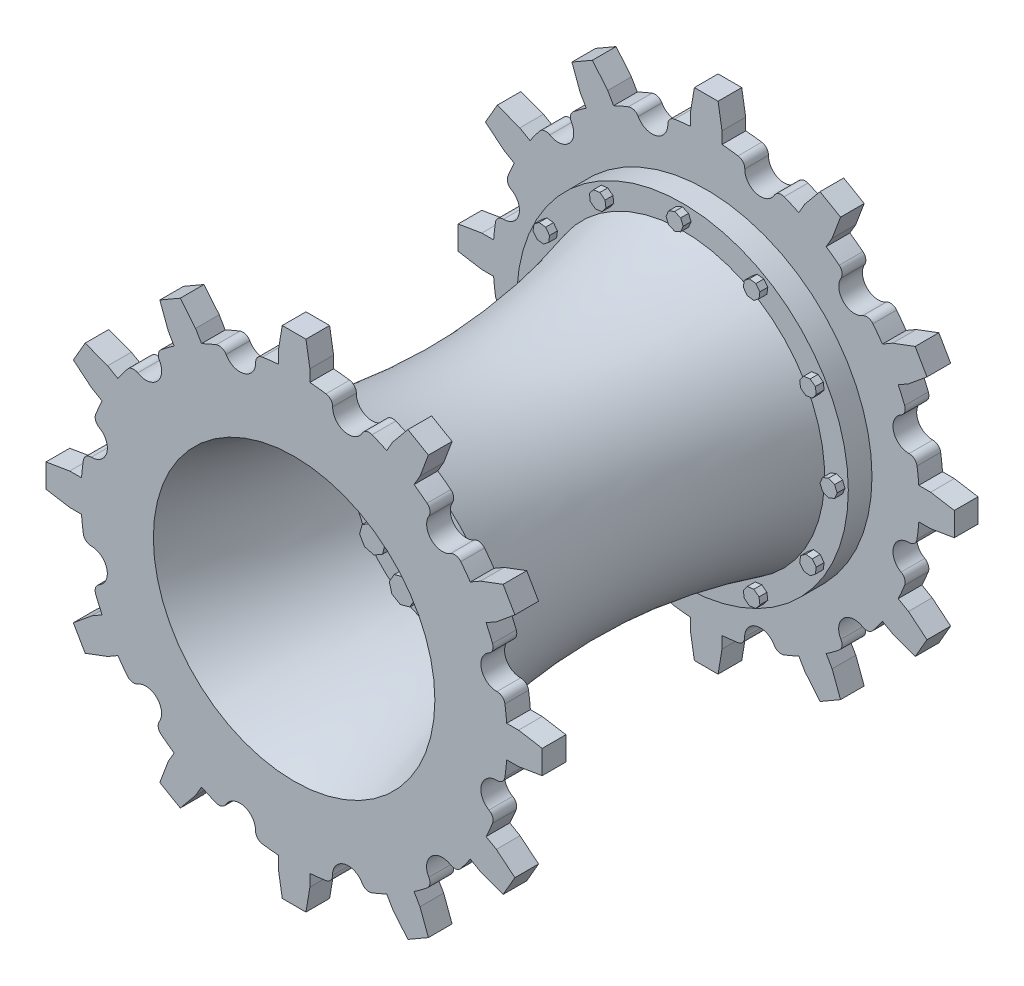
SolidWorks part; units mm, degrees
ref_plane "Ön Düzlem" through (0, 0, 0) normal (0, 0, 1) x (1, 0, 0)
ref_plane "Üst Düzlem" through (0, 0, 0) normal (0, 1, 0) x (1, 0, 0)
ref_plane "Sağ Düzlem" through (0, 0, 0) normal (1, 0, 0) x (0, 0, -1)
sketch "Çizim1" plane through (0, 0, 0) normal (0, 0, 1) x (1, 0, 0)
  line L2 (-20, 269.2582) -> (-20, 284.2582)
  line L3 (20, 269.2582) -> (20, 284.2582)
  line L4 (-20, 284.2582) -> (-15, 314.2582)
  line L5 (-15, 314.2582) -> (15, 314.2582)
  line L6 (15, 314.2582) -> (20, 284.2582)
  line L7 (117.3086, 243.1845) -> (124.8086, 256.1749)
  line L8 (151.9496, 223.1845) -> (159.4496, 236.1749)
  line L9 (124.8086, 256.1749) -> (144.1387, 279.6556)
  line L10 (144.1387, 279.6556) -> (170.1195, 264.6556)
  line L11 (170.1195, 264.6556) -> (159.4496, 236.1749)
  line L13 (223.1845, 151.9496) -> (236.1749, 159.4496)
  line L14 (243.1845, 117.3086) -> (256.1749, 124.8086)
  line L15 (236.1749, 159.4496) -> (264.6556, 170.1195)
  line L16 (264.6556, 170.1195) -> (279.6556, 144.1387)
  line L17 (279.6556, 144.1387) -> (256.1749, 124.8086)
  line L19 (269.2582, 20) -> (284.2582, 20)
  line L20 (269.2582, -20) -> (284.2582, -20)
  line L21 (284.2582, 20) -> (314.2582, 15)
  line L22 (314.2582, 15) -> (314.2582, -15)
  line L23 (314.2582, -15) -> (284.2582, -20)
  line L25 (243.1845, -117.3086) -> (256.1749, -124.8086)
  line L26 (223.1845, -151.9496) -> (236.1749, -159.4496)
  line L27 (256.1749, -124.8086) -> (279.6556, -144.1387)
  line L28 (279.6556, -144.1387) -> (264.6556, -170.1195)
  line L29 (264.6556, -170.1195) -> (236.1749, -159.4496)
  line L31 (151.9496, -223.1845) -> (159.4496, -236.1749)
  line L32 (117.3086, -243.1845) -> (124.8086, -256.1749)
  line L33 (159.4496, -236.1749) -> (170.1195, -264.6556)
  line L34 (170.1195, -264.6556) -> (144.1387, -279.6556)
  line L35 (144.1387, -279.6556) -> (124.8086, -256.1749)
  line L37 (20, -269.2582) -> (20, -284.2582)
  line L38 (-20, -269.2582) -> (-20, -284.2582)
  line L39 (20, -284.2582) -> (15, -314.2582)
  line L40 (15, -314.2582) -> (-15, -314.2582)
  line L41 (-15, -314.2582) -> (-20, -284.2582)
  line L43 (-117.3086, -243.1845) -> (-124.8086, -256.1749)
  line L44 (-151.9496, -223.1845) -> (-159.4496, -236.1749)
  line L45 (-124.8086, -256.1749) -> (-144.1387, -279.6556)
  line L46 (-144.1387, -279.6556) -> (-170.1195, -264.6556)
  line L47 (-170.1195, -264.6556) -> (-159.4496, -236.1749)
  line L49 (-223.1845, -151.9496) -> (-236.1749, -159.4496)
  line L50 (-243.1845, -117.3086) -> (-256.1749, -124.8086)
  line L51 (-236.1749, -159.4496) -> (-264.6556, -170.1195)
  line L52 (-264.6556, -170.1195) -> (-279.6556, -144.1387)
  line L53 (-279.6556, -144.1387) -> (-256.1749, -124.8086)
  line L55 (-269.2582, -20) -> (-284.2582, -20)
  line L56 (-269.2582, 20) -> (-284.2582, 20)
  line L57 (-284.2582, -20) -> (-314.2582, -15)
  line L58 (-314.2582, -15) -> (-314.2582, 15)
  line L59 (-314.2582, 15) -> (-284.2582, 20)
  line L61 (-243.1845, 117.3086) -> (-256.1749, 124.8086)
  line L62 (-223.1845, 151.9496) -> (-236.1749, 159.4496)
  line L63 (-256.1749, 124.8086) -> (-279.6556, 144.1387)
  line L64 (-279.6556, 144.1387) -> (-264.6556, 170.1195)
  line L65 (-264.6556, 170.1195) -> (-236.1749, 159.4496)
  line L67 (-151.9496, 223.1845) -> (-159.4496, 236.1749)
  line L68 (-117.3086, 243.1845) -> (-124.8086, 256.1749)
  line L69 (-159.4496, 236.1749) -> (-170.1195, 264.6556)
  line L70 (-170.1195, 264.6556) -> (-144.1387, 279.6556)
  line L71 (-144.1387, 279.6556) -> (-124.8086, 256.1749)
  line L73 (20, 269.2582) -> (117.6795, 243.8269) construction
  arc A0 (40.3386, 266.9697) -> (20, 269.2582) centre (0, 0) ccw
  arc A1 (48.843, 256.9021) -> (86.3302, 246.8429) centre (68.8397, 256.5425) ccw
  arc A2 (98.7322, 251.3005) -> (86.3302, 246.8429) centre (95.0755, 241.9931) ccw
  arc A3 (48.843, 256.9021) -> (40.3386, 266.9697) centre (38.8446, 257.0819) ccw
  arc A4 (170.7503, 198.0623) -> (168.4191, 211.0332) centre (162.1813, 203.2171) ccw
  arc A5 (170.7503, 198.0623) -> (198.1856, 170.6071) centre (187.8882, 187.7525) ccw
  arc A6 (211.1549, 168.2665) -> (198.1856, 170.6071) centre (203.3343, 162.0344) ccw
  arc A7 (246.9052, 86.1518) -> (251.3718, 98.5506) centre (242.0617, 94.9005) ccw
  arc A8 (246.9052, 86.1518) -> (256.9373, 48.6573) centre (256.5922, 68.6543) ccw
  arc A9 (266.9987, 40.1456) -> (256.9373, 48.6573) centre (257.1099, 38.6588) ccw
  arc A10 (256.9021, -48.843) -> (266.9697, -40.3386) centre (257.0819, -38.8446) ccw
  arc A11 (256.9021, -48.843) -> (246.8429, -86.3302) centre (256.5425, -68.8397) ccw
  arc A12 (251.3005, -98.7322) -> (246.8429, -86.3302) centre (241.9931, -95.0755) ccw
  arc A13 (198.0623, -170.7503) -> (211.0332, -168.4191) centre (203.2171, -162.1813) ccw
  arc A14 (198.0623, -170.7503) -> (170.6071, -198.1856) centre (187.7525, -187.8882) ccw
  arc A15 (168.2665, -211.1549) -> (170.6071, -198.1856) centre (162.0344, -203.3343) ccw
  arc A16 (86.1518, -246.9052) -> (98.5506, -251.3718) centre (94.9005, -242.0617) ccw
  arc A17 (86.1518, -246.9052) -> (48.6573, -256.9373) centre (68.6543, -256.5922) ccw
  arc A18 (40.1456, -266.9987) -> (48.6573, -256.9373) centre (38.6588, -257.1099) ccw
  arc A19 (-48.843, -256.9021) -> (-40.3386, -266.9697) centre (-38.8446, -257.0819) ccw
  arc A20 (-48.843, -256.9021) -> (-86.3302, -246.8429) centre (-68.8397, -256.5425) ccw
  arc A21 (-98.7322, -251.3005) -> (-86.3302, -246.8429) centre (-95.0755, -241.9931) ccw
  arc A22 (-170.7503, -198.0623) -> (-168.4191, -211.0332) centre (-162.1813, -203.2171) ccw
  arc A23 (-170.7503, -198.0623) -> (-198.1856, -170.6071) centre (-187.8882, -187.7525) ccw
  arc A24 (-211.1549, -168.2665) -> (-198.1856, -170.6071) centre (-203.3343, -162.0344) ccw
  arc A25 (-246.9052, -86.1518) -> (-251.3718, -98.5506) centre (-242.0617, -94.9005) ccw
  arc A26 (-246.9052, -86.1518) -> (-256.9373, -48.6573) centre (-256.5922, -68.6543) ccw
  arc A27 (-266.9987, -40.1456) -> (-256.9373, -48.6573) centre (-257.1099, -38.6588) ccw
  arc A28 (-256.9021, 48.843) -> (-266.9697, 40.3386) centre (-257.0819, 38.8446) ccw
  arc A29 (-256.9021, 48.843) -> (-246.8429, 86.3302) centre (-256.5425, 68.8397) ccw
  arc A30 (-251.3005, 98.7322) -> (-246.8429, 86.3302) centre (-241.9931, 95.0755) ccw
  arc A31 (-198.0623, 170.7503) -> (-211.0332, 168.4191) centre (-203.2171, 162.1813) ccw
  arc A32 (-198.0623, 170.7503) -> (-170.6071, 198.1856) centre (-187.7525, 187.8882) ccw
  arc A33 (-168.2665, 211.1549) -> (-170.6071, 198.1856) centre (-162.0344, 203.3343) ccw
  arc A34 (-86.1518, 246.9052) -> (-98.5506, 251.3718) centre (-94.9005, 242.0617) ccw
  arc A35 (-86.1518, 246.9052) -> (-48.6573, 256.9373) centre (-68.6543, 256.5922) ccw
  arc A36 (-40.1456, 266.9987) -> (-48.6573, 256.9373) centre (-38.6588, 257.1099) ccw
  arc A37 (-98.5506, 251.3718) -> (-117.3086, 243.1845) centre (0, 0) ccw
  arc A38 (-211.0332, 168.4191) -> (-223.1845, 151.9496) centre (0, 0) ccw
  arc A39 (-266.9697, 40.3386) -> (-269.2582, 20) centre (0, 0) ccw
  arc A40 (-243.1845, 117.3086) -> (-251.3005, 98.7322) centre (0, 0) ccw
  arc A41 (-151.9496, 223.1845) -> (-168.2665, 211.1549) centre (0, 0) ccw
  arc A42 (-269.2582, -20) -> (-266.9987, -40.1456) centre (0, 0) ccw
  arc A43 (-251.3718, -98.5506) -> (-243.1845, -117.3086) centre (0, 0) ccw
  arc A44 (-223.1845, -151.9496) -> (-211.1549, -168.2665) centre (0, 0) ccw
  arc A45 (-168.4191, -211.0332) -> (-151.9496, -223.1845) centre (0, 0) ccw
  arc A46 (-117.3086, -243.1845) -> (-98.7322, -251.3005) centre (0, 0) ccw
  arc A47 (-40.3386, -266.9697) -> (-20, -269.2582) centre (0, 0) ccw
  arc A48 (20, -269.2582) -> (40.1456, -266.9987) centre (0, 0) ccw
  arc A49 (98.5506, -251.3718) -> (117.3086, -243.1845) centre (0, 0) ccw
  arc A50 (151.9496, -223.1845) -> (168.2665, -211.1549) centre (0, 0) ccw
  arc A51 (211.0332, -168.4191) -> (223.1845, -151.9496) centre (0, 0) ccw
  arc A52 (243.1845, -117.3086) -> (251.3005, -98.7322) centre (0, 0) ccw
  arc A53 (266.9697, -40.3386) -> (269.2582, -20) centre (0, 0) ccw
  arc A54 (269.2582, 20) -> (266.9987, 40.1456) centre (0, 0) ccw
  arc A55 (251.3718, 98.5506) -> (243.1845, 117.3086) centre (0, 0) ccw
  arc A56 (223.1845, 151.9496) -> (211.1549, 168.2665) centre (0, 0) ccw
  arc A57 (168.4191, 211.0332) -> (151.9496, 223.1845) centre (0, 0) ccw
  arc A58 (117.3086, 243.1845) -> (98.7322, 251.3005) centre (0, 0) ccw
  arc A59 (-20, 269.2582) -> (-40.1456, 266.9987) centre (0, 0) ccw
  point P8 (0, 270)
  point P21 (135, 233.8269)
  point P30 (233.8269, 135)
  point P39 (270, 0)
  point P48 (233.8269, -135)
  point P57 (135, -233.8269)
  point P66 (0, -270)
  point P75 (-135, -233.8269)
  point P84 (-233.8269, -135)
  point P93 (-270, 0)
  point P102 (-233.8269, 135)
  point P111 (-135, 233.8269)
  point P117 (0, 0)
  point P200 (0, 0)
  dimension "D1" = 540
  dimension "D8" = 40
  dimension "D9" = 10
  dimension "D3" = 15
  dimension "D4" = 15
  dimension "D5" = 30
  dimension "D6" = 30
  dimension "D7" = 12
  dimension "D10" = 12
extrude "Yükseklik-Ekstrüzyon2" add sketch "Çizim1" along normal blind 30
sketch "Çizim2" plane through (0, 0, 30) normal (0, 0, 1) x (1, 0, 0)
  circle A0 centre (0, 0) radius 210
  dimension "D1" = 420
extrude "Yükseklik-Ekstrüzyon3" add sketch "Çizim2" along normal blind 30
sketch "Çizim3" plane through (0, 0, 60) normal (0, 0, 1) x (1, 0, 0)
  line L0 (-210, 0) -> (-180, 0) construction
  line L1 (-159.5012, 92.088) -> (-158.4198, 100.3014)
  line L2 (-184.1761, 0) -> (-187.3463, 7.6537)
  line L3 (-187.3463, 7.6537) -> (-195, 10.8239)
  line L4 (-195, 10.8239) -> (-202.6537, 7.6537)
  line L5 (-202.6537, 7.6537) -> (-205.8239, 0)
  line L6 (-205.8239, 0) -> (-202.6537, -7.6537)
  line L7 (-202.6537, -7.6537) -> (-195, -10.8239)
  line L8 (-195, -10.8239) -> (-187.3463, -7.6537)
  line L9 (-187.3463, -7.6537) -> (-184.1761, 0)
  line L10 (-158.4198, 100.3014) -> (-163.463, 106.8738)
  line L11 (-163.463, 106.8738) -> (-171.6764, 107.9551)
  line L12 (-171.6764, 107.9551) -> (-178.2487, 102.912)
  line L13 (-178.2487, 102.912) -> (-179.3301, 94.6986)
  line L14 (-179.3301, 94.6986) -> (-174.2869, 88.1262)
  line L15 (-174.2869, 88.1262) -> (-166.0735, 87.0449)
  line L16 (-166.0735, 87.0449) -> (-159.5012, 92.088)
  line L17 (-92.088, 159.5012) -> (-87.0449, 166.0735)
  line L18 (-87.0449, 166.0735) -> (-88.1262, 174.2869)
  line L19 (-88.1262, 174.2869) -> (-94.6986, 179.3301)
  line L20 (-94.6986, 179.3301) -> (-102.912, 178.2487)
  line L21 (-102.912, 178.2487) -> (-107.9551, 171.6764)
  line L22 (-107.9551, 171.6764) -> (-106.8738, 163.463)
  line L23 (-106.8738, 163.463) -> (-100.3014, 158.4198)
  line L24 (-100.3014, 158.4198) -> (-92.088, 159.5012)
  line L25 (0, 184.1761) -> (7.6537, 187.3463)
  line L26 (7.6537, 187.3463) -> (10.8239, 195)
  line L27 (10.8239, 195) -> (7.6537, 202.6537)
  line L28 (7.6537, 202.6537) -> (0, 205.8239)
  line L29 (0, 205.8239) -> (-7.6537, 202.6537)
  line L30 (-7.6537, 202.6537) -> (-10.8239, 195)
  line L31 (-10.8239, 195) -> (-7.6537, 187.3463)
  line L32 (-7.6537, 187.3463) -> (0, 184.1761)
  line L33 (92.088, 159.5012) -> (100.3014, 158.4198)
  line L34 (100.3014, 158.4198) -> (106.8738, 163.463)
  line L35 (106.8738, 163.463) -> (107.9551, 171.6764)
  line L36 (107.9551, 171.6764) -> (102.912, 178.2487)
  line L37 (102.912, 178.2487) -> (94.6986, 179.3301)
  line L38 (94.6986, 179.3301) -> (88.1262, 174.2869)
  line L39 (88.1262, 174.2869) -> (87.0449, 166.0735)
  line L40 (87.0449, 166.0735) -> (92.088, 159.5012)
  line L41 (159.5012, 92.088) -> (166.0735, 87.0449)
  line L42 (166.0735, 87.0449) -> (174.2869, 88.1262)
  line L43 (174.2869, 88.1262) -> (179.3301, 94.6986)
  line L44 (179.3301, 94.6986) -> (178.2487, 102.912)
  line L45 (178.2487, 102.912) -> (171.6764, 107.9551)
  line L46 (171.6764, 107.9551) -> (163.463, 106.8738)
  line L47 (163.463, 106.8738) -> (158.4198, 100.3014)
  line L48 (158.4198, 100.3014) -> (159.5012, 92.088)
  line L49 (184.1761, 0) -> (187.3463, -7.6537)
  line L50 (187.3463, -7.6537) -> (195, -10.8239)
  line L51 (195, -10.8239) -> (202.6537, -7.6537)
  line L52 (202.6537, -7.6537) -> (205.8239, 0)
  line L53 (205.8239, 0) -> (202.6537, 7.6537)
  line L54 (202.6537, 7.6537) -> (195, 10.8239)
  line L55 (195, 10.8239) -> (187.3463, 7.6537)
  line L56 (187.3463, 7.6537) -> (184.1761, 0)
  line L57 (159.5012, -92.088) -> (158.4198, -100.3014)
  line L58 (158.4198, -100.3014) -> (163.463, -106.8738)
  line L59 (163.463, -106.8738) -> (171.6764, -107.9551)
  line L60 (171.6764, -107.9551) -> (178.2487, -102.912)
  line L61 (178.2487, -102.912) -> (179.3301, -94.6986)
  line L62 (179.3301, -94.6986) -> (174.2869, -88.1262)
  line L63 (174.2869, -88.1262) -> (166.0735, -87.0449)
  line L64 (166.0735, -87.0449) -> (159.5012, -92.088)
  line L65 (92.088, -159.5012) -> (87.0449, -166.0735)
  line L66 (87.0449, -166.0735) -> (88.1262, -174.2869)
  line L67 (88.1262, -174.2869) -> (94.6986, -179.3301)
  line L68 (94.6986, -179.3301) -> (102.912, -178.2487)
  line L69 (102.912, -178.2487) -> (107.9551, -171.6764)
  line L70 (107.9551, -171.6764) -> (106.8738, -163.463)
  line L71 (106.8738, -163.463) -> (100.3014, -158.4198)
  line L72 (100.3014, -158.4198) -> (92.088, -159.5012)
  line L73 (0, -184.1761) -> (-7.6537, -187.3463)
  line L74 (-7.6537, -187.3463) -> (-10.8239, -195)
  line L75 (-10.8239, -195) -> (-7.6537, -202.6537)
  line L76 (-7.6537, -202.6537) -> (0, -205.8239)
  line L77 (0, -205.8239) -> (7.6537, -202.6537)
  line L78 (7.6537, -202.6537) -> (10.8239, -195)
  line L79 (10.8239, -195) -> (7.6537, -187.3463)
  line L80 (7.6537, -187.3463) -> (0, -184.1761)
  line L81 (-92.088, -159.5012) -> (-100.3014, -158.4198)
  line L82 (-100.3014, -158.4198) -> (-106.8738, -163.463)
  line L83 (-106.8738, -163.463) -> (-107.9551, -171.6764)
  line L84 (-107.9551, -171.6764) -> (-102.912, -178.2487)
  line L85 (-102.912, -178.2487) -> (-94.6986, -179.3301)
  line L86 (-94.6986, -179.3301) -> (-88.1262, -174.2869)
  line L87 (-88.1262, -174.2869) -> (-87.0449, -166.0735)
  line L88 (-87.0449, -166.0735) -> (-92.088, -159.5012)
  line L89 (-159.5012, -92.088) -> (-166.0735, -87.0449)
  line L90 (-166.0735, -87.0449) -> (-174.2869, -88.1262)
  line L91 (-174.2869, -88.1262) -> (-179.3301, -94.6986)
  line L92 (-179.3301, -94.6986) -> (-178.2487, -102.912)
  line L93 (-178.2487, -102.912) -> (-171.6764, -107.9551)
  line L94 (-171.6764, -107.9551) -> (-163.463, -106.8738)
  line L95 (-163.463, -106.8738) -> (-158.4198, -100.3014)
  line L96 (-158.4198, -100.3014) -> (-159.5012, -92.088)
  circle A0 centre (0, 0) radius 180 construction
  circle A1 centre (0, 0) radius 210 construction
  circle A2 centre (0, 0) radius 210 construction
  circle A3 centre (0, 0) radius 195 construction
  circle A4 centre (-195, 0) radius 10 construction
  circle A5 centre (-168.875, 97.5) radius 10 construction
  circle A6 centre (-97.5, 168.875) radius 10 construction
  circle A7 centre (0, 195) radius 10 construction
  circle A8 centre (97.5, 168.875) radius 10 construction
  circle A9 centre (168.875, 97.5) radius 10 construction
  circle A10 centre (195, 0) radius 10 construction
  circle A11 centre (168.875, -97.5) radius 10 construction
  circle A12 centre (97.5, -168.875) radius 10 construction
  circle A13 centre (0, -195) radius 10 construction
  circle A14 centre (-97.5, -168.875) radius 10 construction
  circle A15 centre (-168.875, -97.5) radius 10 construction
  point P10 (-195, 0)
  point P134 (0, 0)
  dimension "D1" = 360
  dimension "D2" = 20
  dimension "D3" = 12
extrude "Yükseklik-Ekstrüzyon4" add sketch "Çizim3" along normal blind 10
ref_plane "Düzlem1" through (0, 0, 252) normal (0, 0, 1) x (1, 0, 0)
sketch "Çizim15" plane through (0, 0, 0) normal (0, 0, -1) x (-1, 0, 0)
  circle A0 centre (0, 0) radius 45
  dimension "D1" = 90
extrude "Kes-Ekstrüzyon2" cut sketch "Çizim15" against normal blind 768
sketch "Çizim17" plane through (0, 0, 0) normal (1, 0, 0) x (0, 0, -1)
  line L0 (0, 0) -> (-776.2338, 0) construction
  line L1 (-60, 45) -> (-276, 45)
  line L2 (-60, 210) -> (-60, -210) construction
  line L3 (-276, 45) -> (-276, 150)
  line L4 (-60, 180) -> (-60, 45)
  arc A0 (-276, 150) -> (-60, 180) centre (-276, 942.6) ccw
  dimension "D1" = 180
  dimension "D2" = 45
  dimension "D3" = 216
  dimension "D4" = 150
revolve "Döndür2" add sketch "Çizim17" angle 360 about L0
mirror "Aynalama5" about plane through (0, 45, 276) normal (0, 0, 1) of bodies 121
sketch "Çizim18" plane through (0, 0, 0) normal (1, 0, 0) x (0, 0, -1)
  line L1 (-252, 0) -> (-642.2, 0)
  line L2 (-642.2, 0) -> (-642.2, 217.1923)
  line L3 (-252, 231) -> (-252, -231) construction
  line L4 (-252, 0) -> (-252, 130.3545)
  arc A2 (-497.4504, 160.757) -> (-54.5496, 160.757) centre (-276, 942.6) ccw
  arc A3 (-642.2, 217.1923) -> (-252, 130.3545) centre (-276, 942.6) ccw
  dimension "D1" = 20
revolve "Kes-Döndür2" cut sketch "Çizim18" angle 360 about L1
sketch "Çizim19" plane through (0, 0, 252) normal (0, 0, 1) x (1, 0, 0)
  circle A1 centre (0, 0) radius 130.3545
  circle A2 centre (0, 0) radius 130.3545
  dimension "D1" = 0
extrude "Yükseklik-Ekstrüzyon8" add sketch "Çizim19" along normal blind 96 contours A2
sketch "Çizim20" plane through (0, 0, 348) normal (0, 0, 1) x (1, 0, 0)
  line L0 (0, 130.3545) -> (0, 75) construction
  line L1 (67.4356, 86.8019) -> (64.2194, 98.8049)
  line L2 (15, 108.8905) -> (6.2132, 117.6772)
  line L3 (6.2132, 117.6772) -> (-6.2132, 117.6772)
  line L4 (-6.2132, 117.6772) -> (-15, 108.8905)
  line L5 (-15, 108.8905) -> (-15, 96.464)
  line L6 (-15, 96.464) -> (-6.2132, 87.6772)
  line L7 (-6.2132, 87.6772) -> (6.2132, 87.6772)
  line L8 (6.2132, 87.6772) -> (15, 96.464)
  line L9 (15, 96.464) -> (15, 108.8905)
  line L10 (64.2194, 98.8049) -> (53.4578, 105.0181)
  line L11 (53.4578, 105.0181) -> (41.4548, 101.8019)
  line L12 (41.4548, 101.8019) -> (35.2416, 91.0403)
  line L13 (35.2416, 91.0403) -> (38.4578, 79.0373)
  line L14 (38.4578, 79.0373) -> (49.2194, 72.8241)
  line L15 (49.2194, 72.8241) -> (61.2224, 76.0403)
  line L16 (61.2224, 76.0403) -> (67.4356, 86.8019)
  line L17 (101.8019, 41.4548) -> (105.0181, 53.4578)
  line L18 (105.0181, 53.4578) -> (98.8049, 64.2194)
  line L19 (98.8049, 64.2194) -> (86.8019, 67.4356)
  line L20 (86.8019, 67.4356) -> (76.0403, 61.2224)
  line L21 (76.0403, 61.2224) -> (72.8241, 49.2194)
  line L22 (72.8241, 49.2194) -> (79.0373, 38.4578)
  line L23 (79.0373, 38.4578) -> (91.0403, 35.2416)
  line L24 (91.0403, 35.2416) -> (101.8019, 41.4548)
  line L25 (108.8905, -15) -> (117.6772, -6.2132)
  line L26 (117.6772, -6.2132) -> (117.6772, 6.2132)
  line L27 (117.6772, 6.2132) -> (108.8905, 15)
  line L28 (108.8905, 15) -> (96.464, 15)
  line L29 (96.464, 15) -> (87.6772, 6.2132)
  line L30 (87.6772, 6.2132) -> (87.6772, -6.2132)
  line L31 (87.6772, -6.2132) -> (96.464, -15)
  line L32 (96.464, -15) -> (108.8905, -15)
  line L33 (86.8019, -67.4356) -> (98.8049, -64.2194)
  line L34 (98.8049, -64.2194) -> (105.0181, -53.4578)
  line L35 (105.0181, -53.4578) -> (101.8019, -41.4548)
  line L36 (101.8019, -41.4548) -> (91.0403, -35.2416)
  line L37 (91.0403, -35.2416) -> (79.0373, -38.4578)
  line L38 (79.0373, -38.4578) -> (72.8241, -49.2194)
  line L39 (72.8241, -49.2194) -> (76.0403, -61.2224)
  line L40 (76.0403, -61.2224) -> (86.8019, -67.4356)
  line L41 (41.4548, -101.8019) -> (53.4578, -105.0181)
  line L42 (53.4578, -105.0181) -> (64.2194, -98.8049)
  line L43 (64.2194, -98.8049) -> (67.4356, -86.8019)
  line L44 (67.4356, -86.8019) -> (61.2224, -76.0403)
  line L45 (61.2224, -76.0403) -> (49.2194, -72.8241)
  line L46 (49.2194, -72.8241) -> (38.4578, -79.0373)
  line L47 (38.4578, -79.0373) -> (35.2416, -91.0403)
  line L48 (35.2416, -91.0403) -> (41.4548, -101.8019)
  line L49 (-15, -108.8905) -> (-6.2132, -117.6772)
  line L50 (-6.2132, -117.6772) -> (6.2132, -117.6772)
  line L51 (6.2132, -117.6772) -> (15, -108.8905)
  line L52 (15, -108.8905) -> (15, -96.464)
  line L53 (15, -96.464) -> (6.2132, -87.6772)
  line L54 (6.2132, -87.6772) -> (-6.2132, -87.6772)
  line L55 (-6.2132, -87.6772) -> (-15, -96.464)
  line L56 (-15, -96.464) -> (-15, -108.8905)
  line L57 (-67.4356, -86.8019) -> (-64.2194, -98.8049)
  line L58 (-64.2194, -98.8049) -> (-53.4578, -105.0181)
  line L59 (-53.4578, -105.0181) -> (-41.4548, -101.8019)
  line L60 (-41.4548, -101.8019) -> (-35.2416, -91.0403)
  line L61 (-35.2416, -91.0403) -> (-38.4578, -79.0373)
  line L62 (-38.4578, -79.0373) -> (-49.2194, -72.8241)
  line L63 (-49.2194, -72.8241) -> (-61.2224, -76.0403)
  line L64 (-61.2224, -76.0403) -> (-67.4356, -86.8019)
  line L65 (-101.8019, -41.4548) -> (-105.0181, -53.4578)
  line L66 (-105.0181, -53.4578) -> (-98.8049, -64.2194)
  line L67 (-98.8049, -64.2194) -> (-86.8019, -67.4356)
  line L68 (-86.8019, -67.4356) -> (-76.0403, -61.2224)
  line L69 (-76.0403, -61.2224) -> (-72.8241, -49.2194)
  line L70 (-72.8241, -49.2194) -> (-79.0373, -38.4578)
  line L71 (-79.0373, -38.4578) -> (-91.0403, -35.2416)
  line L72 (-91.0403, -35.2416) -> (-101.8019, -41.4548)
  line L73 (-108.8905, 15) -> (-117.6772, 6.2132)
  line L74 (-117.6772, 6.2132) -> (-117.6772, -6.2132)
  line L75 (-117.6772, -6.2132) -> (-108.8905, -15)
  line L76 (-108.8905, -15) -> (-96.464, -15)
  line L77 (-96.464, -15) -> (-87.6772, -6.2132)
  line L78 (-87.6772, -6.2132) -> (-87.6772, 6.2132)
  line L79 (-87.6772, 6.2132) -> (-96.464, 15)
  line L80 (-96.464, 15) -> (-108.8905, 15)
  line L81 (-86.8019, 67.4356) -> (-98.8049, 64.2194)
  line L82 (-98.8049, 64.2194) -> (-105.0181, 53.4578)
  line L83 (-105.0181, 53.4578) -> (-101.8019, 41.4548)
  line L84 (-101.8019, 41.4548) -> (-91.0403, 35.2416)
  line L85 (-91.0403, 35.2416) -> (-79.0373, 38.4578)
  line L86 (-79.0373, 38.4578) -> (-72.8241, 49.2194)
  line L87 (-72.8241, 49.2194) -> (-76.0403, 61.2224)
  line L88 (-76.0403, 61.2224) -> (-86.8019, 67.4356)
  line L89 (-41.4548, 101.8019) -> (-53.4578, 105.0181)
  line L90 (-53.4578, 105.0181) -> (-64.2194, 98.8049)
  line L91 (-64.2194, 98.8049) -> (-67.4356, 86.8019)
  line L92 (-67.4356, 86.8019) -> (-61.2224, 76.0403)
  line L93 (-61.2224, 76.0403) -> (-49.2194, 72.8241)
  line L94 (-49.2194, 72.8241) -> (-38.4578, 79.0373)
  line L95 (-38.4578, 79.0373) -> (-35.2416, 91.0403)
  line L96 (-35.2416, 91.0403) -> (-41.4548, 101.8019)
  circle A0 centre (0, 0) radius 75
  circle A1 centre (0, 0) radius 130.3545 construction
  circle A2 centre (0, 102.6772) radius 15 construction
  circle A3 centre (51.3386, 88.9211) radius 15 construction
  circle A4 centre (88.9211, 51.3386) radius 15 construction
  circle A5 centre (102.6772, 0) radius 15 construction
  circle A6 centre (88.9211, -51.3386) radius 15 construction
  circle A7 centre (51.3386, -88.9211) radius 15 construction
  circle A8 centre (0, -102.6772) radius 15 construction
  circle A9 centre (-51.3386, -88.9211) radius 15 construction
  circle A10 centre (-88.9211, -51.3386) radius 15 construction
  circle A11 centre (-102.6772, 0) radius 15 construction
  circle A12 centre (-88.9211, 51.3386) radius 15 construction
  circle A13 centre (-51.3386, 88.9211) radius 15 construction
  point P129 (0, 0)
  dimension "D1" = 150
  dimension "D2" = 30
  dimension "D3" = 12
extrude "Yükseklik-Ekstrüzyon12" add sketch "Çizim20" along normal blind 16
sketch "Çizim23" plane through (0, 0, 364) normal (0, 0, 1) x (1, 0, 0)
  circle A0 centre (0, 0) radius 75
extrude "Yükseklik-Ekstrüzyon13" add sketch "Çizim23" along normal blind 15
fillet "Radyus3" radius 40 1 edges at (75, 0, 379)
